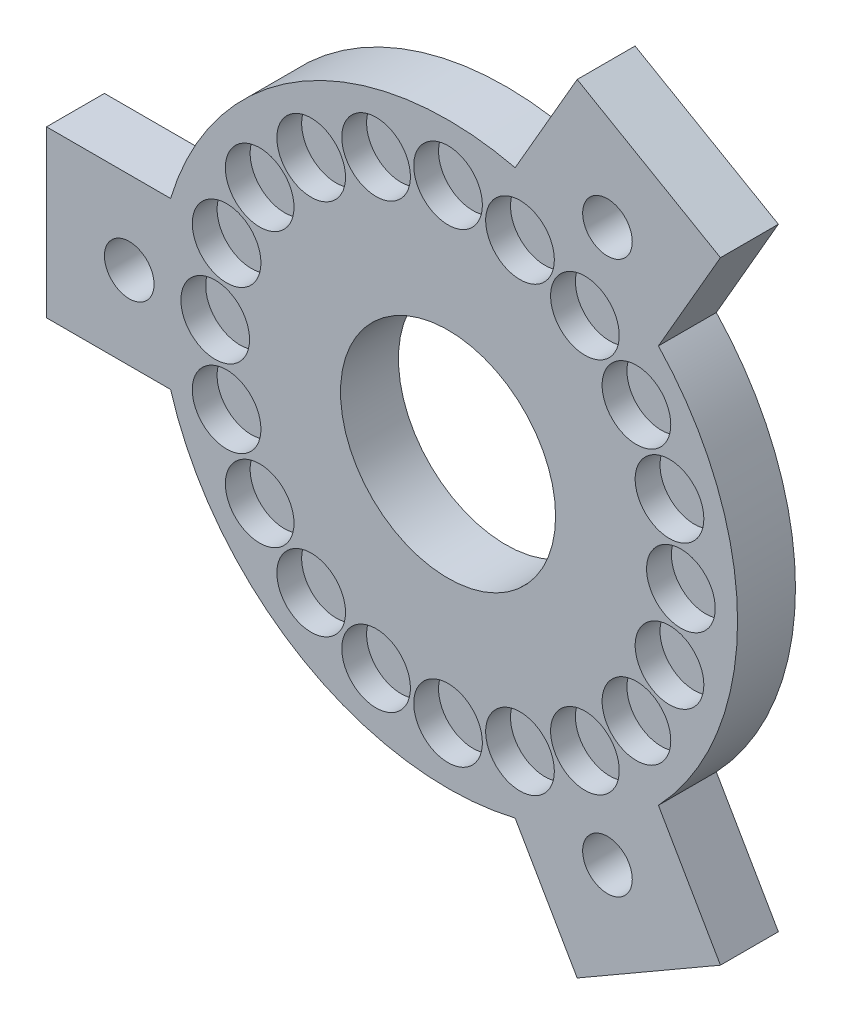
SolidWorks part; units mm, degrees
ref_plane "Ebene vorne" through (0, 0, 0) normal (0, 0, 1) x (1, 0, 0)
ref_plane "Ebene oben" through (0, 0, 0) normal (0, 1, 0) x (1, 0, 0)
ref_plane "Ebene rechts" through (0, 0, 0) normal (1, 0, 0) x (0, 0, -1)
sketch "Skizze1" plane through (0, 0, 0) normal (0, 0, 1) x (1, 0, 0)
  circle A0 centre (0, 0) radius 28.15
  circle A1 centre (0, 28.15) radius 4.3077
  circle A2 centre (8.6988, 26.7722) radius 4.3077
  circle A3 centre (16.5462, 22.7738) radius 4.3077
  circle A4 centre (22.7738, 16.5462) radius 4.3077
  circle A5 centre (26.7722, 8.6988) radius 4.3077
  circle A6 centre (28.15, 0) radius 4.3077
  circle A7 centre (26.7722, -8.6988) radius 4.3077
  circle A8 centre (22.7738, -16.5462) radius 4.3077
  circle A9 centre (16.5462, -22.7738) radius 4.3077
  circle A10 centre (8.6988, -26.7722) radius 4.3077
  circle A11 centre (0, -28.15) radius 4.3077
  circle A12 centre (-8.6988, -26.7722) radius 4.3077
  circle A13 centre (-16.5462, -22.7738) radius 4.3077
  circle A14 centre (-22.7738, -16.5462) radius 4.3077
  circle A15 centre (-26.7722, -8.6988) radius 4.3077
  circle A16 centre (-28.15, 0) radius 4.3077
  circle A17 centre (-26.7722, 8.6988) radius 4.3077
  circle A18 centre (-22.7738, 16.5462) radius 4.3077
  circle A19 centre (-16.5462, 22.7738) radius 4.3077
  circle A20 centre (-8.6988, 26.7722) radius 4.3077
  circle A21 centre (0, 0) radius 35
  point P46 (0, 0)
  dimension "D1" = 20
  dimension "D2" = 70
  dimension "D3" = 56.3
extrude "Aufsatz-Linear austragen3" add sketch "Skizze1" along normal blind 7 contours A21
sketch "Skizze3" plane through (0, 0, 7) normal (0, 0, 1) x (1, 0, 0)
  circle A0 centre (0, 0) radius 28.15
  circle A1 centre (0, 28.15) radius 4.15
  circle A2 centre (8.6988, 26.7722) radius 4.15
  circle A3 centre (16.5462, 22.7738) radius 4.15
  circle A4 centre (22.7738, 16.5462) radius 4.15
  circle A5 centre (26.7722, 8.6988) radius 4.15
  circle A6 centre (28.15, 0) radius 4.15
  circle A7 centre (26.7722, -8.6988) radius 4.15
  circle A8 centre (22.7738, -16.5462) radius 4.15
  circle A9 centre (16.5462, -22.7738) radius 4.15
  circle A10 centre (8.6988, -26.7722) radius 4.15
  circle A11 centre (0, -28.15) radius 4.15
  circle A12 centre (-8.6988, -26.7722) radius 4.15
  circle A13 centre (-16.5462, -22.7738) radius 4.15
  circle A14 centre (-22.7738, -16.5462) radius 4.15
  circle A15 centre (-26.7722, -8.6988) radius 4.15
  circle A16 centre (-28.15, 0) radius 4.15
  circle A17 centre (-26.7722, 8.6988) radius 4.15
  circle A18 centre (-22.7738, 16.5462) radius 4.15
  circle A19 centre (-16.5462, 22.7738) radius 4.15
  circle A20 centre (-8.6988, 26.7722) radius 4.15
  point P46 (0, 0)
  dimension "D1" = 20
  dimension "D2" = 56.3
  dimension "D3" = 8.3
extrude "Schnitt-Linear austragen1" cut sketch "Skizze3" against normal blind 3 contours A0 A8 | A0 A8 | A0 A3 | A0 A3 | A10 | A9 | A7 | A6 | A5 | A4 | A2 | A1 | A20 | A19 | A18 | A17 | A16 | A15 | A14 | A13 | A12 | A11 region at (24.1533, -17.5484, 7) region at (21.3053, -15.4792, 7) region at (15.4792, 21.3053, 7) region at (17.5484, 24.1533, 7)
sketch "Skizze4" plane through (0, 0, 7) normal (0, 0, 1) x (1, 0, 0)
  circle A0 centre (0, 0) radius 13
  dimension "D1" = 26
extrude "Schnitt-Linear austragen2" cut sketch "Skizze4" against normal up to next
ref_plane "Ebene1" through (0, 0, 0) normal (0, 0, -1) x (-1, 0, 0)
sketch "Skizze6" plane through (0, 0, 0) normal (0, 0, -1) x (-1, 0, 0)
  line L0 (-15.6103, -47.0378) -> (-32.9308, -37.0378)
  line L5 (48.541, 10) -> (33.541, 10)
  line L6 (48.541, 10) -> (48.541, -10)
  line L7 (48.541, -10) -> (33.541, -10)
  line L8 (33.541, 10) -> (33.541, -10)
  line L9 (-15.6103, -47.0378) -> (-8.1103, -34.0474)
  line L10 (-8.1103, -34.0474) -> (-25.4308, -24.0474)
  line L11 (-32.9308, -37.0378) -> (-25.4308, -24.0474)
  line L12 (-32.9308, 37.0378) -> (-15.6103, 47.0378)
  line L13 (-32.9308, 37.0378) -> (-25.4308, 24.0474)
  line L14 (-25.4308, 24.0474) -> (-8.1103, 34.0474)
  line L15 (-15.6103, 47.0378) -> (-8.1103, 34.0474)
  circle A0 centre (0, 0) radius 35 construction
  point P18 (0, 0)
  dimension "D1" = 3
  dimension "D3" = 20
  dimension "D4" = 15
  dimension "D5" = 10
extrude "Aufsatz-Linear austragen4" add sketch "Skizze6" against normal blind 7
sketch "Skizze9" plane through (0, 0, 0) normal (0, 0, -1) x (-1, 0, 0)
  line L0 (48.541, -10) -> (48.541, 10) construction
  line L1 (-8.1103, 34.0474) -> (-15.6103, 47.0378) construction
  line L2 (-15.6103, 47.0378) -> (-32.9308, 37.0378) construction
  circle A0 centre (38.541, 0) radius 3
  circle A1 centre (-19.2705, -33.3775) radius 3
  circle A2 centre (-19.2705, 33.3775) radius 3
  point P11 (0, 0)
  dimension "D1" = 10
  dimension "D3" = 6
  dimension "D4" = 10
  dimension "D5" = 10
  dimension "D2" = 3
extrude "Schnitt-Linear austragen5" cut sketch "Skizze9" against normal up to next
